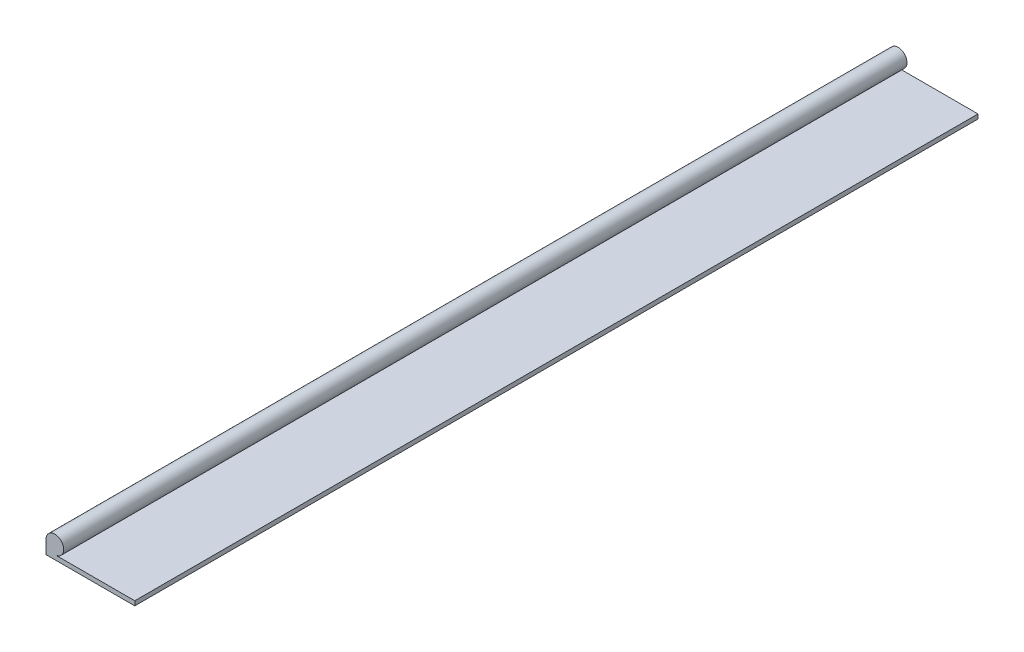
SolidWorks part; units mm, degrees
material "AISI 316 Annealed Stainless Steel Bar (SS)"
ref_plane "Front Plane" through (0, 0, 0) normal (0, 0, 1) x (1, 0, 0)
ref_plane "Top Plane" through (0, 0, 0) normal (0, 1, 0) x (1, 0, 0)
ref_plane "Right Plane" through (0, 0, 0) normal (1, 0, 0) x (0, 0, -1)
sketch "Sketch1" plane through (0, 0, 0) normal (0, 0, 1) x (1, 0, 0)
  line L0 (-25.4, 1.27) -> (-25.4, 3.81)
  line L5 (0, 0) -> (-25.4, 0)
  line L6 (0, 0) -> (0, 1.27)
  line L7 (0, 1.27) -> (-22.86, 1.27)
  line L8 (-25.4, 0) -> (-25.4, 1.27)
  arc A0 (-22.86, 1.27) -> (-25.4, 3.81) centre (-22.86, 3.81) ccw
  dimension "D3" = 5.08
  dimension "D5" = 2.54
  dimension "D1" = 25.4
  dimension "D2" = 1.27
extrude "Boss-Extrude2" add sketch "Sketch1" along normal blind 241.3
ref_plane "Plane1" through (-22.86, 0, 0) normal (1, 0, 0) x (0, 0, -1)
ref_plane "Plane2" through (0, 3.175, 0) normal (0, 1, 0) x (1, 0, 0)
ref_axis "Axis1" through (-22.86, 3.175, -12.065) along (0, 0, 1)
